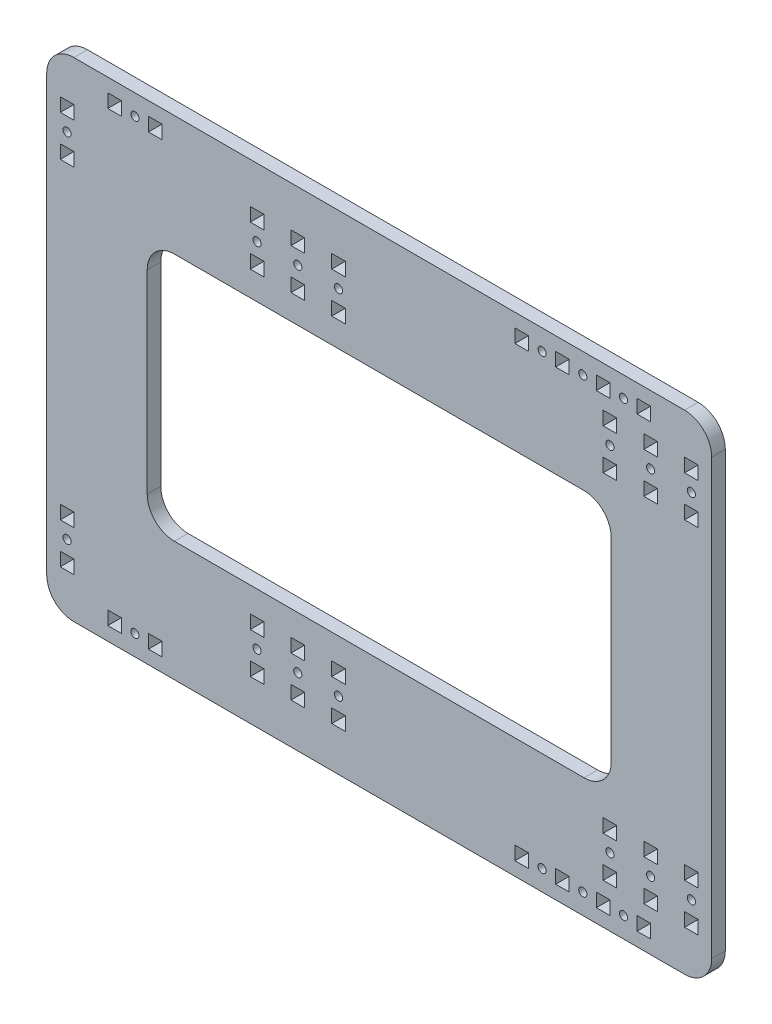
SolidWorks part; units mm, degrees
ref_plane "Front Plane" through (0, 0, 0) normal (0, 0, 1) x (1, 0, 0)
ref_plane "Top Plane" through (0, 0, 0) normal (0, 1, 0) x (1, 0, 0)
ref_plane "Right Plane" through (0, 0, 0) normal (1, 0, 0) x (0, 0, -1)
sketch "Sketch1" plane through (0, 0, 0) normal (0, 0, 1) x (1, 0, 0)
  line L0 (0, 0) -> (264.3375, 0) construction
  line L1 (-91.3244, 90) -> (153.676, 90)
  line L5 (23.6756, 97.7888) -> (23.6756, -107.1048) construction
  line L6 (-92.4996, 82.5) -> (92.5, 82.5) construction
  line L7 (92.5, -82.5) -> (-92.4996, -82.5) construction
  line L8 (-91.3244, 90) -> (-91.3244, -90)
  line L51 (-83.8244, 77.0051) -> (-83.8244, -67.4641) construction
  line L105 (-91.3244, -90) -> (153.676, -90)
  line L106 (31.1758, 123.2986) -> (31.1758, -104.5367) construction
  line L107 (-54.2991, -45.812) -> (116.6507, -45.812)
  line L108 (-54.2991, -45.812) -> (-54.2991, 45.812)
  line L111 (-54.2991, 45.812) -> (116.6507, 45.812)
  line L114 (116.6507, -45.812) -> (116.6507, 45.812)
  line L117 (-54.2991, -45.812) -> (116.6507, 45.812) construction
  line L122 (153.676, 90) -> (153.676, -90)
  line L124 (-83.8244, 65) -> (153.676, 65) construction
  line L125 (-83.8244, -65) -> (153.676, -65) construction
  line L126 (-54.2991, 45.812) -> (116.6507, -45.812) construction
  point P1 (31.1758, 0)
  point P17 (0, 0)
  point P26 (127.5, -49.75)
  line B0 (-63.8248, 82.5) -> (-53.8248, 82.5) construction
  line B1 (-63.8248, 85) -> (-68.8248, 85)
  line B2 (-63.8248, 85) -> (-63.8248, 80)
  line B3 (-63.8248, 80) -> (-68.8248, 80)
  line B4 (-68.8248, 85) -> (-68.8248, 80)
  line B5 (-53.8248, 85) -> (-48.8248, 85)
  line B6 (-53.8248, 85) -> (-53.8248, 80)
  line B7 (-53.8248, 80) -> (-48.8248, 80)
  line B8 (-48.8248, 85) -> (-48.8248, 80)
  line B9 (-58.8248, 82.5) -> (-58.8248, 89.4724) construction
  circle B10 centre (-58.8248, 82.5) radius 1.5
  line B11 (111.176, 82.5) -> (101.176, 82.5) construction
  line B12 (111.176, 85) -> (116.176, 85)
  line B13 (111.176, 85) -> (111.176, 80)
  line B14 (111.176, 80) -> (116.176, 80)
  line B15 (116.176, 85) -> (116.176, 80)
  line B16 (101.176, 85) -> (96.176, 85)
  line B17 (101.176, 85) -> (101.176, 80)
  line B18 (101.176, 80) -> (96.176, 80)
  line B19 (96.176, 85) -> (96.176, 80)
  line B20 (106.176, 82.5) -> (106.176, 89.4724) construction
  circle B21 centre (106.176, 82.5) radius 1.5
  line B22 (111.176, -82.5) -> (101.176, -82.5) construction
  line B23 (111.176, -85) -> (116.176, -85)
  line B24 (111.176, -85) -> (111.176, -80)
  line B25 (111.176, -80) -> (116.176, -80)
  line B26 (116.176, -85) -> (116.176, -80)
  line B27 (101.176, -85) -> (96.176, -85)
  line B28 (101.176, -85) -> (101.176, -80)
  line B29 (101.176, -80) -> (96.176, -80)
  line B30 (96.176, -85) -> (96.176, -80)
  line B31 (106.176, -82.5) -> (106.176, -89.4724) construction
  circle B32 centre (106.176, -82.5) radius 1.5
  line B33 (-63.8248, -82.5) -> (-53.8248, -82.5) construction
  line B34 (-63.8248, -85) -> (-68.8248, -85)
  line B35 (-63.8248, -85) -> (-63.8248, -80)
  line B36 (-63.8248, -80) -> (-68.8248, -80)
  line B37 (-68.8248, -85) -> (-68.8248, -80)
  line B38 (-53.8248, -85) -> (-48.8248, -85)
  line B39 (-53.8248, -85) -> (-53.8248, -80)
  line B40 (-53.8248, -80) -> (-48.8248, -80)
  line B41 (-48.8248, -85) -> (-48.8248, -80)
  line B42 (-58.8248, -82.5) -> (-58.8248, -89.4724) construction
  circle B43 centre (-58.8248, -82.5) radius 1.5
  line B44 (96.176, 82.5) -> (86.176, 82.5) construction
  line B45 (96.176, 85) -> (101.176, 85)
  line B46 (96.176, 85) -> (96.176, 80)
  line B47 (96.176, 80) -> (101.176, 80)
  line B48 (101.176, 85) -> (101.176, 80)
  line B49 (86.176, 85) -> (81.176, 85)
  line B50 (86.176, 85) -> (86.176, 80)
  line B51 (86.176, 80) -> (81.176, 80)
  line B52 (81.176, 85) -> (81.176, 80)
  line B53 (91.176, 82.5) -> (91.176, 89.4724) construction
  circle B54 centre (91.176, 82.5) radius 1.5
  line B55 (126.176, 82.5) -> (116.176, 82.5) construction
  line B56 (126.176, 85) -> (131.176, 85)
  line B57 (126.176, 85) -> (126.176, 80)
  line B58 (126.176, 80) -> (131.176, 80)
  line B59 (131.176, 85) -> (131.176, 80)
  line B60 (116.176, 85) -> (111.176, 85)
  line B61 (116.176, 85) -> (116.176, 80)
  line B62 (116.176, 80) -> (111.176, 80)
  line B63 (111.176, 85) -> (111.176, 80)
  line B64 (121.176, 82.5) -> (121.176, 89.4724) construction
  circle B65 centre (121.176, 82.5) radius 1.5
  line B66 (96.176, -82.5) -> (86.176, -82.5) construction
  line B67 (96.176, -85) -> (101.176, -85)
  line B68 (96.176, -85) -> (96.176, -80)
  line B69 (96.176, -80) -> (101.176, -80)
  line B70 (101.176, -85) -> (101.176, -80)
  line B71 (86.176, -85) -> (81.176, -85)
  line B72 (86.176, -85) -> (86.176, -80)
  line B73 (86.176, -80) -> (81.176, -80)
  line B74 (81.176, -85) -> (81.176, -80)
  line B75 (91.176, -82.5) -> (91.176, -89.4724) construction
  circle B76 centre (91.176, -82.5) radius 1.5
  line B77 (126.176, -82.5) -> (116.176, -82.5) construction
  line B78 (126.176, -85) -> (131.176, -85)
  line B79 (126.176, -85) -> (126.176, -80)
  line B80 (126.176, -80) -> (131.176, -80)
  line B81 (131.176, -85) -> (131.176, -80)
  line B82 (116.176, -85) -> (111.176, -85)
  line B83 (116.176, -85) -> (116.176, -80)
  line B84 (116.176, -80) -> (111.176, -80)
  line B85 (111.176, -85) -> (111.176, -80)
  line B86 (121.176, -82.5) -> (121.176, -89.4724) construction
  circle B87 centre (121.176, -82.5) radius 1.5
  line B88 (-83.8244, 70) -> (-83.8244, 60) construction
  line B89 (-86.3244, 70) -> (-86.3244, 75)
  line B90 (-86.3244, 70) -> (-81.3244, 70)
  line B91 (-81.3244, 70) -> (-81.3244, 75)
  line B92 (-86.3244, 75) -> (-81.3244, 75)
  line B93 (-86.3244, 60) -> (-86.3244, 55)
  line B94 (-86.3244, 60) -> (-81.3244, 60)
  line B95 (-81.3244, 60) -> (-81.3244, 55)
  line B96 (-86.3244, 55) -> (-81.3244, 55)
  line B97 (-83.8244, 65) -> (-90.7968, 65) construction
  circle B98 centre (-83.8244, 65) radius 1.5
  line B99 (-83.8244, -60) -> (-83.8244, -70) construction
  line B100 (-86.3244, -60) -> (-86.3244, -55)
  line B101 (-86.3244, -60) -> (-81.3244, -60)
  line B102 (-81.3244, -60) -> (-81.3244, -55)
  line B103 (-86.3244, -55) -> (-81.3244, -55)
  line B104 (-86.3244, -70) -> (-86.3244, -75)
  line B105 (-86.3244, -70) -> (-81.3244, -70)
  line B106 (-81.3244, -70) -> (-81.3244, -75)
  line B107 (-86.3244, -75) -> (-81.3244, -75)
  line B108 (-83.8244, -65) -> (-90.7968, -65) construction
  circle B109 centre (-83.8244, -65) radius 1.5
  line B110 (146.176, 70) -> (146.176, 60) construction
  line B111 (143.676, 70) -> (143.676, 75)
  line B112 (143.676, 70) -> (148.676, 70)
  line B113 (148.676, 70) -> (148.676, 75)
  line B114 (143.676, 75) -> (148.676, 75)
  line B115 (143.676, 60) -> (143.676, 55)
  line B116 (143.676, 60) -> (148.676, 60)
  line B117 (148.676, 60) -> (148.676, 55)
  line B118 (143.676, 55) -> (148.676, 55)
  line B119 (146.176, 65) -> (139.2036, 65) construction
  circle B120 centre (146.176, 65) radius 1.5
  line B121 (146.176, -60) -> (146.176, -70) construction
  line B122 (143.676, -60) -> (143.676, -55)
  line B123 (143.676, -60) -> (148.676, -60)
  line B124 (148.676, -60) -> (148.676, -55)
  line B125 (143.676, -55) -> (148.676, -55)
  line B126 (143.676, -70) -> (143.676, -75)
  line B127 (143.676, -70) -> (148.676, -70)
  line B128 (148.676, -70) -> (148.676, -75)
  line B129 (143.676, -75) -> (148.676, -75)
  line B130 (146.176, -65) -> (139.2036, -65) construction
  circle B131 centre (146.176, -65) radius 1.5
  line B132 (131.176, -60) -> (131.176, -70) construction
  line B133 (128.676, -60) -> (128.676, -55)
  line B134 (128.676, -60) -> (133.676, -60)
  line B135 (133.676, -60) -> (133.676, -55)
  line B136 (128.676, -55) -> (133.676, -55)
  line B137 (128.676, -70) -> (128.676, -75)
  line B138 (128.676, -70) -> (133.676, -70)
  line B139 (133.676, -70) -> (133.676, -75)
  line B140 (128.676, -75) -> (133.676, -75)
  line B141 (131.176, -65) -> (124.2036, -65) construction
  circle B142 centre (131.176, -65) radius 1.5
  line B143 (116.176, -60) -> (116.176, -70) construction
  line B144 (113.676, -60) -> (113.676, -55)
  line B145 (113.676, -60) -> (118.676, -60)
  line B146 (118.676, -60) -> (118.676, -55)
  line B147 (113.676, -55) -> (118.676, -55)
  line B148 (113.676, -70) -> (113.676, -75)
  line B149 (113.676, -70) -> (118.676, -70)
  line B150 (118.676, -70) -> (118.676, -75)
  line B151 (113.676, -75) -> (118.676, -75)
  line B152 (116.176, -65) -> (109.2036, -65) construction
  circle B153 centre (116.176, -65) radius 1.5
  line B154 (131.176, 70) -> (131.176, 60) construction
  line B155 (128.676, 70) -> (128.676, 75)
  line B156 (128.676, 70) -> (133.676, 70)
  line B157 (133.676, 70) -> (133.676, 75)
  line B158 (128.676, 75) -> (133.676, 75)
  line B159 (128.676, 60) -> (128.676, 55)
  line B160 (128.676, 60) -> (133.676, 60)
  line B161 (133.676, 60) -> (133.676, 55)
  line B162 (128.676, 55) -> (133.676, 55)
  line B163 (131.176, 65) -> (124.2036, 65) construction
  circle B164 centre (131.176, 65) radius 1.5
  line B165 (116.176, 70) -> (116.176, 60) construction
  line B166 (113.676, 70) -> (113.676, 75)
  line B167 (113.676, 70) -> (118.676, 70)
  line B168 (118.676, 70) -> (118.676, 75)
  line B169 (113.676, 75) -> (118.676, 75)
  line B170 (113.676, 60) -> (113.676, 55)
  line B171 (113.676, 60) -> (118.676, 60)
  line B172 (118.676, 60) -> (118.676, 55)
  line B173 (113.676, 55) -> (118.676, 55)
  line B174 (116.176, 65) -> (109.2036, 65) construction
  circle B175 centre (116.176, 65) radius 1.5
  line B176 (16.1756, -60) -> (16.1756, -70) construction
  line B177 (13.6756, -60) -> (13.6756, -55)
  line B178 (13.6756, -60) -> (18.6756, -60)
  line B179 (18.6756, -60) -> (18.6756, -55)
  line B180 (13.6756, -55) -> (18.6756, -55)
  line B181 (13.6756, -70) -> (13.6756, -75)
  line B182 (13.6756, -70) -> (18.6756, -70)
  line B183 (18.6756, -70) -> (18.6756, -75)
  line B184 (13.6756, -75) -> (18.6756, -75)
  line B185 (16.1756, -65) -> (9.2032, -65) construction
  circle B186 centre (16.1756, -65) radius 1.5
  line B187 (1.1756, -60) -> (1.1756, -70) construction
  line B188 (-1.3244, -60) -> (-1.3244, -55)
  line B189 (-1.3244, -60) -> (3.6756, -60)
  line B190 (3.6756, -60) -> (3.6756, -55)
  line B191 (-1.3244, -55) -> (3.6756, -55)
  line B192 (-1.3244, -70) -> (-1.3244, -75)
  line B193 (-1.3244, -70) -> (3.6756, -70)
  line B194 (3.6756, -70) -> (3.6756, -75)
  line B195 (-1.3244, -75) -> (3.6756, -75)
  line B196 (1.1756, -65) -> (-5.7968, -65) construction
  circle B197 centre (1.1756, -65) radius 1.5
  line B198 (-13.8244, -60) -> (-13.8244, -70) construction
  line B199 (-16.3244, -60) -> (-16.3244, -55)
  line B200 (-16.3244, -60) -> (-11.3244, -60)
  line B201 (-11.3244, -60) -> (-11.3244, -55)
  line B202 (-16.3244, -55) -> (-11.3244, -55)
  line B203 (-16.3244, -70) -> (-16.3244, -75)
  line B204 (-16.3244, -70) -> (-11.3244, -70)
  line B205 (-11.3244, -70) -> (-11.3244, -75)
  line B206 (-16.3244, -75) -> (-11.3244, -75)
  line B207 (-13.8244, -65) -> (-20.7968, -65) construction
  circle B208 centre (-13.8244, -65) radius 1.5
  line B209 (16.1756, 60) -> (16.1756, 70) construction
  line B210 (13.6756, 60) -> (13.6756, 55)
  line B211 (13.6756, 60) -> (18.6756, 60)
  line B212 (18.6756, 60) -> (18.6756, 55)
  line B213 (13.6756, 55) -> (18.6756, 55)
  line B214 (13.6756, 70) -> (13.6756, 75)
  line B215 (13.6756, 70) -> (18.6756, 70)
  line B216 (18.6756, 70) -> (18.6756, 75)
  line B217 (13.6756, 75) -> (18.6756, 75)
  line B218 (16.1756, 65) -> (9.2032, 65) construction
  circle B219 centre (16.1756, 65) radius 1.5
  line B220 (1.1756, 60) -> (1.1756, 70) construction
  line B221 (-1.3244, 60) -> (-1.3244, 55)
  line B222 (-1.3244, 60) -> (3.6756, 60)
  line B223 (3.6756, 60) -> (3.6756, 55)
  line B224 (-1.3244, 55) -> (3.6756, 55)
  line B225 (-1.3244, 70) -> (-1.3244, 75)
  line B226 (-1.3244, 70) -> (3.6756, 70)
  line B227 (3.6756, 70) -> (3.6756, 75)
  line B228 (-1.3244, 75) -> (3.6756, 75)
  line B229 (1.1756, 65) -> (-5.7968, 65) construction
  circle B230 centre (1.1756, 65) radius 1.5
  line B231 (-13.8244, 60) -> (-13.8244, 70) construction
  line B232 (-16.3244, 60) -> (-16.3244, 55)
  line B233 (-16.3244, 60) -> (-11.3244, 60)
  line B234 (-11.3244, 60) -> (-11.3244, 55)
  line B235 (-16.3244, 55) -> (-11.3244, 55)
  line B236 (-16.3244, 70) -> (-16.3244, 75)
  line B237 (-16.3244, 70) -> (-11.3244, 70)
  line B238 (-11.3244, 70) -> (-11.3244, 75)
  line B239 (-16.3244, 75) -> (-11.3244, 75)
  line B240 (-13.8244, 65) -> (-20.7968, 65) construction
  circle B241 centre (-13.8244, 65) radius 1.5
  dimension "D1" = 165
  dimension "D2" = 7.5
  dimension "D3" = 15
  dimension "D4" = 32.4996
  dimension "D5" = 32.5
  dimension "D6" = 7.5
  dimension "D7" = 15
  dimension "D9" = 115
  dimension "D10" = 23.6756
  dimension "D13" = 7.5
  dimension "D14" = 25
  dimension "D18" = 7.5
  dimension "D19" = 15
  dimension "D20" = 15
sketch_block_instance "Trou M3 plots 5mm-1"
sketch_block "Trou M3 plots 5mm" parameters "D2"=3, "D1"=5, "D3"=5, "D4"=10
sketch_block_instance "Trou M3 plots 5mm-3"
sketch_block_instance "Trou M3 plots 5mm-4"
sketch_block_instance "Trou M3 plots 5mm-5"
sketch_block_instance "Trou M3 plots 5mm-15"
sketch_block_instance "Trou M3 plots 5mm-16"
sketch_block_instance "Trou M3 plots 5mm-18"
sketch_block_instance "Trou M3 plots 5mm-19"
sketch_block_instance "Trou M3 plots 5mm-20"
sketch_block_instance "Trou M3 plots 5mm-21"
sketch_block_instance "Trou M3 plots 5mm-22"
sketch_block_instance "Trou M3 plots 5mm-23"
sketch_block_instance "Trou M3 plots 5mm-24"
sketch_block_instance "Trou M3 plots 5mm-25"
sketch_block_instance "Trou M3 plots 5mm-26"
sketch_block_instance "Trou M3 plots 5mm-27"
sketch_block_instance "Trou M3 plots 5mm-28"
sketch_block_instance "Trou M3 plots 5mm-29"
sketch_block_instance "Trou M3 plots 5mm-30"
sketch_block_instance "Trou M3 plots 5mm-34"
sketch_block_instance "Trou M3 plots 5mm-35"
sketch_block_instance "Trou M3 plots 5mm-36"
extrude "Boss-Extrude1" add sketch "Sketch1" along normal blind 5 contours L122 L1 L8 L105 B87 B81 B78 B79 B80 B76 B56 B59 B58 B57 B54 B52 B49 B50 B51 region at (31.1758, 86.9598, 0)
fillet "Fillet1" radius 10 8 edges at (153.676, 90, 2.5) (153.676, -90, 2.5) (-91.3244, -90, 2.5) (-91.3244, 90, 2.5) (-54.2991, -45.812, 2.5) (116.6507, -45.812, 2.5) (116.6507, 45.812, 2.5) (-54.2991, 45.812, 2.5)
